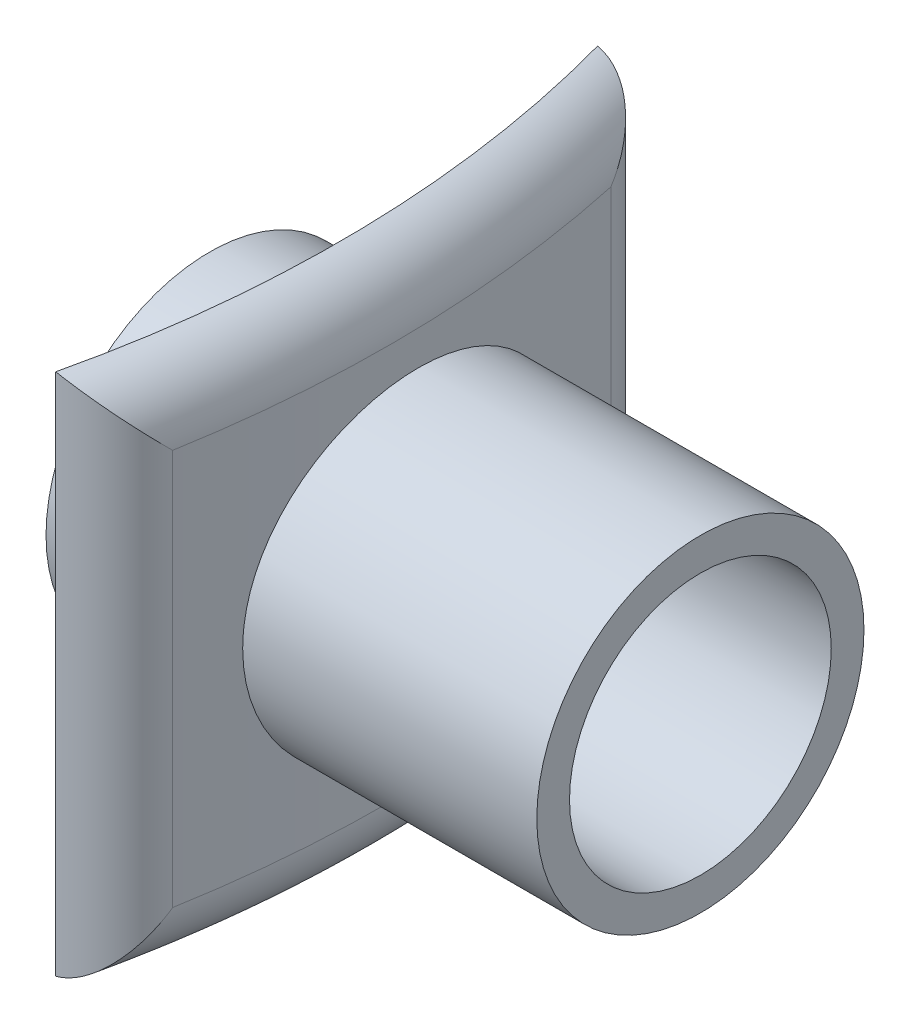
SolidWorks part; units mm, degrees
ref_plane "Front Plane" through (0, 0, 0) normal (0, 0, 1) x (1, 0, 0)
ref_plane "Top Plane" through (0, 0, 0) normal (0, 1, 0) x (1, 0, 0)
ref_plane "Right Plane" through (0, 0, 0) normal (1, 0, 0) x (0, 0, -1)
sketch "Sketch3" plane through (0, 0, 0) normal (1, 0, 0) x (0, 0, -1)
  circle A0 centre (0, 0) radius 5
  circle A1 centre (0, 0) radius 3.3
  dimension "D1" = 10
  dimension "D2" = 6.6
extrude "Boss-Extrude3" add sketch "Sketch3" along normal blind 15 contours A1 | A0 region at (0, 0, 0)
sketch "Sketch6" plane through (0, 0, 0) normal (0, 1, 0) x (1, 0, 0)
  line L1 (3.4775, 8.3808) -> (4.92, 8.9783)
  line L2 (3.8195, -8.5225) -> (5.27, -9.1233)
  arc A0 (3.8195, -8.5225) -> (3.4775, 8.3808) centre (-29.5351, -0.7421) ccw
  arc A1 (5.27, -9.1233) -> (4.92, 8.9783) centre (-29.5351, -0.7421) ccw
  circle A2 centre (-29.5351, -0.7421) radius 34.25 construction
  circle A3 centre (-29.5351, -0.7421) radius 35.8 construction
  dimension "D1" = 1.55
extrude "Boss-Extrude4" add sketch "Sketch6" along normal blind 8 and the other way blind 8 contours L2 A1 L1 A0
sketch "Sketch7" plane through (0, 0, 0) normal (-1, 0, 0) x (0, 0, 1)
  circle A0 centre (0, 0) radius 4
  dimension "D1" = 8
extrude "Cut-Extrude1" cut sketch "Sketch7" against normal up to surface (15 mm away) from offset 1 up to face at (15, 0, -5) offset against normal yes
fillet "Fillet2" radius 2 4 edges at (6.2582, 8, 0.05) (4.92, 0, -8.9783) (6.2582, -8, 0.05) (5.27, 0, 9.1233)
